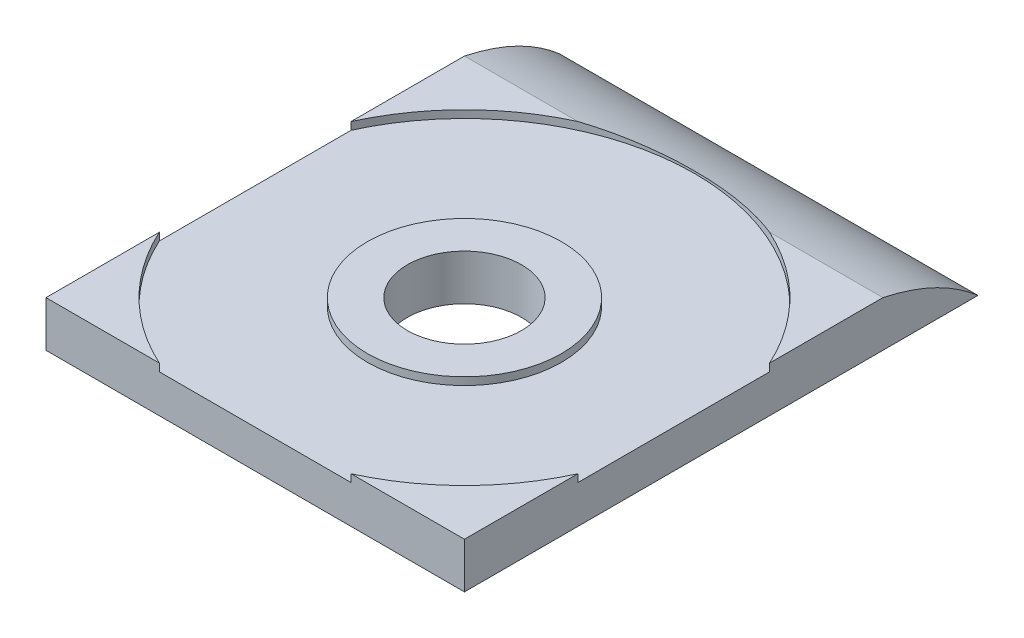
SolidWorks part; units mm, degrees
note: The reader was unsure of these and kept them because the rebuilt part matched: shared geometry of "Sketch1<4>".
ref_plane "Front Plane" through (0, 0, 0) normal (0, 0, 1) x (1, 0, 0)
ref_plane "Top Plane" through (0, 0, 0) normal (0, 1, 0) x (1, 0, 0)
ref_plane "Right Plane" through (0, 0, 0) normal (1, 0, 0) x (0, 0, -1)
sketch "Sketch1" plane through (0, 0, 0) normal (0, 1, 0) x (1, 0, 0)
  line L0 (0, 0) -> (-5.5, 0)
  line L1 (0, 0) -> (5.5, 0)
  line L2 (-5.5, 5.5) -> (-5.5, -5.5)
  line L3 (5.5, 5.5) -> (5.5, -5.5)
  line L4 (-5.5, -5.5) -> (5.5, -5.5)
  line L5 (-5.5, 5.5) -> (5.5, 5.5)
  line L6 (-5.5, 5.5) -> (-5.5, 8)
  line L7 (5.5, 5.5) -> (5.5, 8)
  line L8 (-5.5, 8) -> (5.5, 8)
  circle A0 centre (0, 0) radius 1.5
  dimension "D1" = 3
  dimension "D2" = 5.5
  dimension "D3" = 5.5
  dimension "D4" = 5.5
  dimension "D5" = 2.5
extrude "Boss-Extrude1" add sketch "Sketch1" along normal blind 1.2 contours A0 L1 L3 L5 L2 L0 | A0 L0 L2 L4 L3 L1
extrude "Boss-Extrude2" add sketch "Sketch1<4>" along normal blind 1.2 contours L8 L6 L5 L7
sketch "Sketch1<4>" plane through (0, 0, 0) normal (0, 1, 0) x (1, 0, 0) same geometry as "Sketch1"
sketch "Sketch2" plane through (0, 1.2, 0) normal (0, 1, 0) x (1, 0, 0)
  line L1 (-5.5, 8) -> (5.5, 8)
  line L2 (-5.5, 8) -> (-5.5, 5.5)
  line L3 (-5.5, 5.5) -> (5.5, 5.5)
  line L4 (5.5, 8) -> (5.5, 5.5)
sketch "Sketch3" plane through (5.5, 0, 0) normal (1, 0, 0) x (0, 0, -1)
  line L1 (8, 1.2) -> (5.5, 1.2) construction
  line L2 (8, 1.2) -> (5.5, 1.2) construction
  line L3 (5.5, 1.2) -> (8, 1.2)
  line L5 (8, 1.2) -> (8, 0)
  spline S0 degree 2 poles (5.5, 1.2) (8.4498, 0.569) (9.4989, -2.2498) knots 0 0 0 1 1 1
extrude "Cut-Extrude1" cut sketch "Sketch3" against normal through all
sketch "Sketch4" plane through (0, 1.2, 0) normal (0, 1, 0) x (1, 0, 0)
  circle A0 centre (0, 0) radius 6.05
  circle A1 centre (0, 0) radius 2.55
  dimension "D1" = 12.1
  dimension "D2" = 5.1
extrude "Cut-Extrude3" cut sketch "Sketch4" against normal blind 0.2
